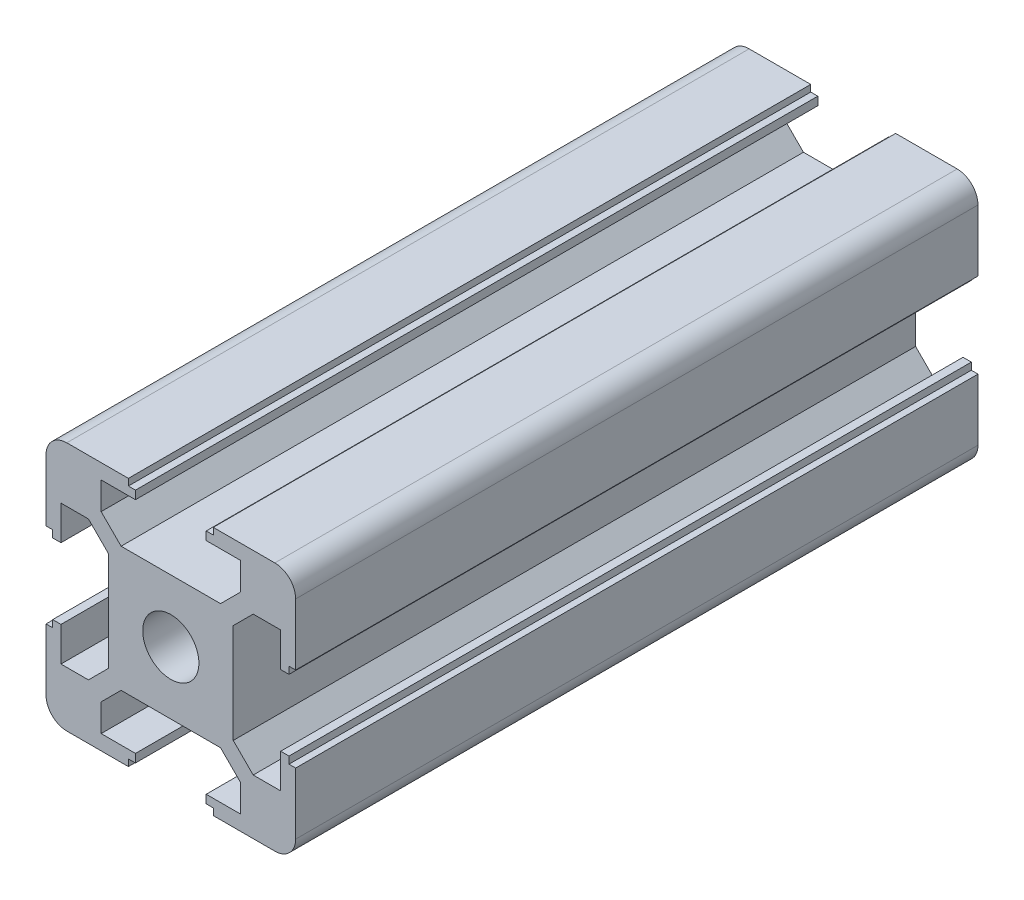
SolidWorks part; units mm, degrees
ref_plane "Front Plane" through (0, 0, 0) normal (0, 0, 1) x (1, 0, 0)
ref_plane "Top Plane" through (0, 0, 0) normal (0, 1, 0) x (1, 0, 0)
ref_plane "Right Plane" through (0, 0, 0) normal (1, 0, 0) x (0, 0, -1)
sketch "Sketch1" plane through (0, 0, 0) normal (0, 0, 1) x (1, 0, 0)
  line L1 (-15, -15) -> (15, -15)
  line L2 (-15, -15) -> (-15, 15)
  line L3 (-15, 15) -> (15, 15)
  line L4 (15, -15) -> (15, 15)
  line L5 (-15, -15) -> (15, 15) construction
  line L6 (-15, 15) -> (15, -15) construction
  point P0 (0, 0)
  dimension "D1" = 30
  dimension "D2" = 30
extrude "Boss-Extrude1" add sketch "Sketch1" along normal mid plane 82
sketch "Sketch2" plane through (0, 0, 41) normal (0, 0, 1) x (1, 0, 0)
  circle A0 centre (0, 0) radius 3.375
  dimension "D1" = 6.75
extrude "Cut-Extrude1" cut sketch "Sketch2" against normal through all
cosmetic thread "Cosmetic Thread1" parameters "D1"=12, "D2"=8
cosmetic thread "Cosmetic Thread2" parameters "D1"=12, "D2"=8
fillet "Fillet1" radius 2.5 4 edges at (15, -15, 0) (-15, -15, 0) (15, 15, 0) (-15, 15, 0)
sketch "Sketch3" plane through (0, 0, 41) normal (0, 0, 1) x (1, 0, 0)
  line L0 (0, -1000) -> (0, 49000) construction
  line L1 (0, 15) -> (-5.1, 15)
  line L2 (12.5, 15) -> (-12.5, 15) construction
  line L3 (-5.1, 15) -> (-5.1, 14.2)
  line L4 (-5.1, 14.2) -> (-4.25, 14.2)
  line L5 (-4.25, 14.2) -> (-4.25, 13.2)
  line L6 (-4.25, 13.2) -> (-8.375, 13.2)
  line L7 (-8.375, 13.2) -> (-8.375, 9.9)
  line L8 (-8.375, 9.9) -> (-5.975, 7.5)
  line L9 (-5.975, 7.5) -> (0, 7.5)
  line L10 (0, 7.5) -> (0, 15)
  dimension "D1" = 5.1
  dimension "D2" = 4.25
  dimension "D3" = 1.8
  dimension "D4" = 1
  dimension "D5" = 3.3
  dimension "D6" = 8.375
  dimension "D7" = 135
  dimension "D8" = 7.5
extrude "Cut-Extrude2" cut sketch "Sketch3" against normal through all
mirror "Mirror1" about plane through (0, 0, 0) normal (1, 0, 0) of "Cut-Extrude2"
pattern_circular "CirPattern1" count 4 over 360 about axis through (0, 0, -41) along (0, 0, 1) of "Mirror1"
